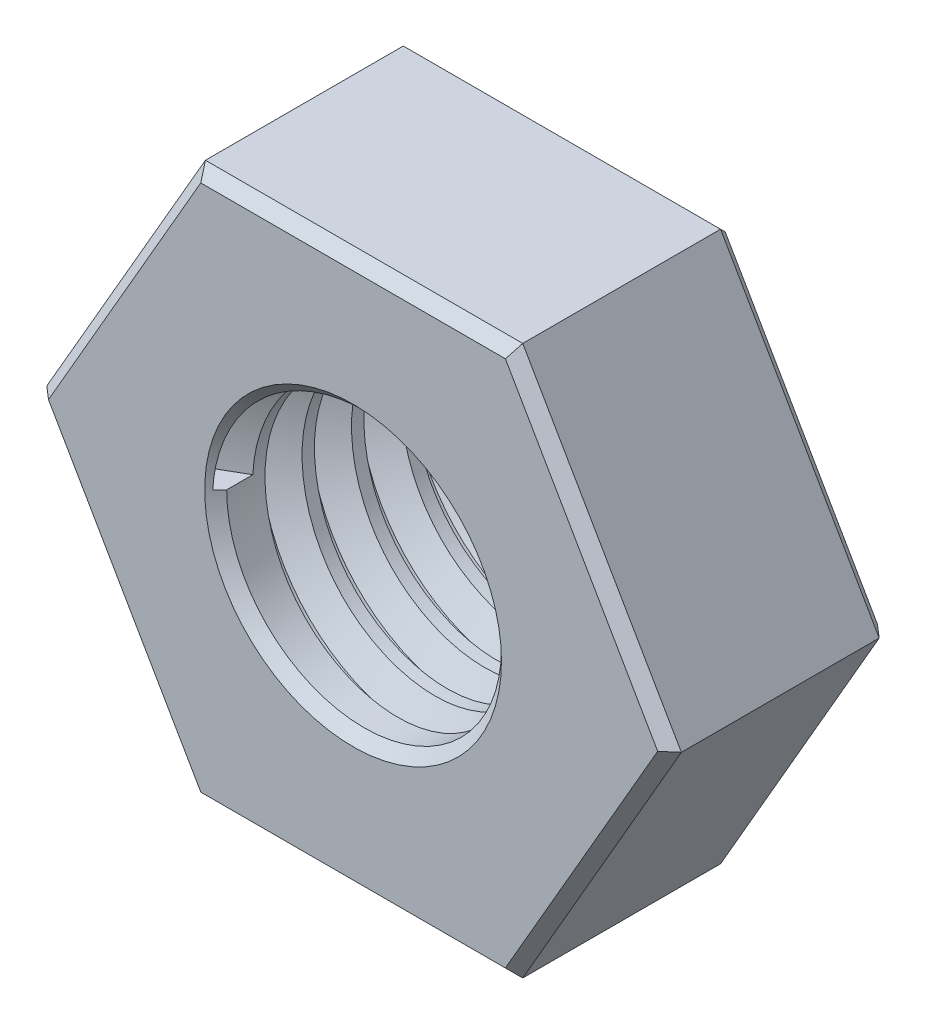
SolidWorks part; units mm, degrees
ref_plane "Front" through (0, 0, 0) normal (0, 0, 1) x (1, 0, 0)
ref_plane "Top" through (0, 0, 0) normal (0, 1, 0) x (1, 0, 0)
ref_plane "Right" through (0, 0, 0) normal (1, 0, 0) x (0, 0, -1)
sketch "Sketch1" plane through (0, 0, 0) normal (0, 0, 1) x (1, 0, 0)
  line L1 (2.8868, 0) -> (1.4434, 2.5)
  line L2 (1.4434, 2.5) -> (-1.4434, 2.5)
  line L3 (-1.4434, 2.5) -> (-2.8868, 0)
  line L4 (-2.8868, 0) -> (-1.4434, -2.5)
  line L5 (-1.4434, -2.5) -> (1.4434, -2.5)
  line L6 (1.4434, -2.5) -> (2.8868, 0)
  circle A0 centre (0, 0) radius 2.5 construction
  circle A1 centre (0, 0) radius 1.25
  dimension "D1" = 5
  dimension "D2" = 2.5
extrude "Boss-Extrude1" add sketch "Sketch1" along normal blind 2
thread "Thread1" pitch 0.45 method cut profile "Thread Profile1" start angle 0, offset 0, length 2, pitch 0.45, diameter 2.5
ref_plane "Plane1" through (-1.25, 0, 2) normal (0, -1, 0) x (-1, 0, 0)
sketch "Thread Profile1" plane through (-1.25, 0, 2) normal (0, -1, 0) x (-1, 0, 0)
  line L0 (0, 0) -> (0, 0.45) construction
  line L1 (0, 0) -> (0.2436, 0.1406)
  line L2 (0.2436, 0.1406) -> (0.2436, 0.1969)
  line L3 (0.2436, 0.1969) -> (0, 0.3375)
  line L4 (0.2436, 0.1687) -> (0, 0.1687) construction
  line L11 (0, 0) -> (0, 0.3375)
  point P2 (0, 0)
  dimension "Pitch" = 0.45
  dimension "Profile_Angle" = 60
  dimension "Profile_Land" = 0.0562
  dimension "Profile_Height" = 0.2436
chamfer "Chamfer1" distance 0.1 angle 45 7 edges at (-1.25, 0, 2) (0, -2.5, 2) (-2.1651, -1.25, 2) (-2.1651, 1.25, 2) (0, 2.5, 2) (2.1651, 1.25, 2) (2.1651, -1.25, 2)
chamfer "Chamfer2" distance 0.1 angle 45 6 edges at (2.1651, 1.25, 0) (2.1651, -1.25, 0) (0, -2.5, 0) (-2.1651, -1.25, 0) (-2.1651, 1.25, 0) (0, 2.5, 0)
